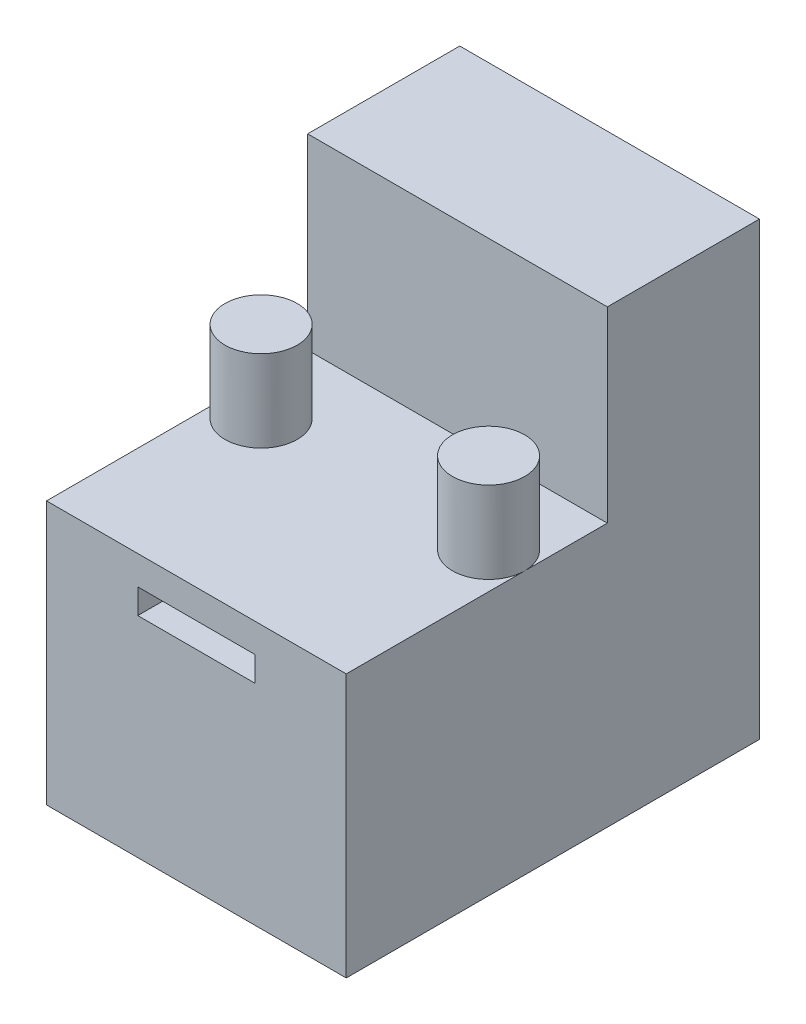
SolidWorks part; units mm, degrees
ref_plane "Front Plane" through (0, 0, 0) normal (0, 0, 1) x (1, 0, 0)
ref_plane "Top Plane" through (0, 0, 0) normal (0, 1, 0) x (1, 0, 0)
ref_plane "Right Plane" through (0, 0, 0) normal (1, 0, 0) x (0, 0, -1)
ref_axis "X-Axis" through (-88.99, 0, 0) along (1, 0, 0)
ref_axis "Y-Axis" through (0, 55, 0) along (0, -1, 0)
ref_axis "Z-Axis" through (0, 0, -88.99) along (0, 0, 1)
sketch "Sketch1" plane through (0, 0, 0) normal (0, 1, 0) x (1, 0, 0)
  line L1 (-6.6, 9.1) -> (6.6, 9.1)
  line L2 (-6.6, 9.1) -> (-6.6, -9.1)
  line L3 (-6.6, -9.1) -> (6.6, -9.1)
  line L4 (6.6, 9.1) -> (6.6, -9.1)
  line L5 (-6.6, 9.1) -> (6.6, -9.1) construction
  line L6 (-6.6, -9.1) -> (6.6, 9.1) construction
  point P0 (0, 0)
  dimension "D1" = 18.2
  dimension "D2" = 13.2
extrude "Boss-Extrude1" add sketch "Sketch1" along normal blind 11.6
sketch "Sketch2" plane through (0, 11.6, 0) normal (0, 1, 0) x (1, 0, 0)
  line L0 (-5.01, -9.1) -> (-5.01, 9.1) construction
  line L1 (-6.6, -9.1) -> (6.6, -9.1) construction
  line L2 (6.6, 9.1) -> (-6.6, 9.1) construction
  line L3 (-6.6, 9.1) -> (-6.6, -9.1) construction
  circle A0 centre (-5.01, -1.24) radius 1.59
  point P8 (-5.01, 0.35)
  point P9 (-6.6, -1.24)
  dimension "D2" = 3.18
  dimension "D1" = 9.45
  dimension "D3" = 0
extrude "Boss-Extrude2" add sketch "Sketch2" along normal blind 3.6
mirror "Mirror1" about plane through (0, 0, 0) normal (1, 0, 0) of "Boss-Extrude2"
sketch "Sketch3" plane through (0, 11.6, 0) normal (0, 1, 0) x (1, 0, 0)
  line L0 (6.6, -1.24) -> (6.6, 9.1) construction
  line L1 (-6.6, 9.1) -> (6.6, 9.1)
  line L2 (-6.6, 9.1) -> (-6.6, 2.4)
  line L3 (-6.6, 2.4) -> (6.6, 2.4)
  line L4 (6.6, 9.1) -> (6.6, 2.4)
  dimension "D1" = 6.7
extrude "Boss-Extrude3" add sketch "Sketch3" along normal blind 8.25
sketch "Sketch4" plane through (0, 0, 9.1) normal (0, 0, 1) x (1, 0, 0)
  line L0 (0, 11.6) -> (0, 0) construction
  line L1 (-6.6, 11.6) -> (6.6, 11.6) construction
  line L3 (-2.5825, 9.2325) -> (2.5825, 9.2325)
  line L4 (-2.5825, 9.2325) -> (-2.5825, 10.329)
  line L5 (-2.5825, 10.329) -> (2.5825, 10.329)
  line L6 (2.5825, 9.2325) -> (2.5825, 10.329)
  line L7 (-2.5825, 9.2325) -> (2.5825, 10.329) construction
  line L8 (-2.5825, 10.329) -> (2.5825, 9.2325) construction
  point P5 (0, 9.7807)
extrude "Cut-Extrude1" cut sketch "Sketch4" against normal blind 5
